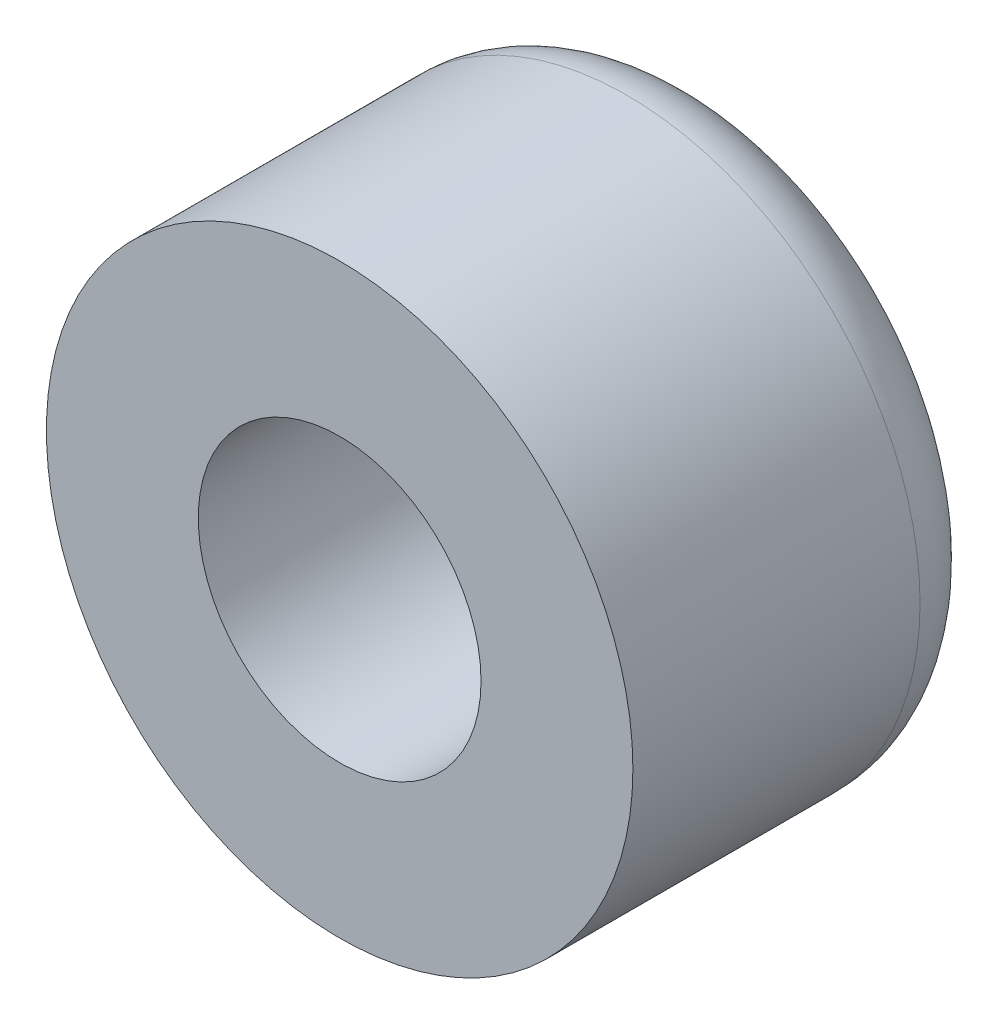
SolidWorks part; units mm, degrees
material "0.6010 (EN-GJL-100)"
ref_plane "Alzado" through (0, 0, 0) normal (0, 0, 1) x (1, 0, 0)
ref_plane "Planta" through (0, 0, 0) normal (0, 1, 0) x (1, 0, 0)
ref_plane "Vista lateral" through (0, 0, 0) normal (1, 0, 0) x (0, 0, -1)
sketch "Croquis2" plane through (0, 0, 0) normal (0, 0, 1) x (1, 0, 0)
  circle A0 centre (0, 0) radius 12.6
  circle A1 centre (0, 0) radius 6.075
  circle A2 centre (0, 0) radius 12.6 construction
  arc A3 (5.9997, -0.0555) -> (4.075, 4.4039) centre (0, 0) ccw construction
  dimension "D1" = 0.075
extrude "Saliente-Extruir1" add sketch "Croquis2" against normal up to surface (15.6 mm away)
fillet "Redondeo1" 2 edges at (-12.6, 0, -15.6) (-6.075, 0, -15.6) type full round first side face at (12.6, 0, 0) second side face at (6.075, 0, 0) middle face at (-12.6, 0, -15.6)
